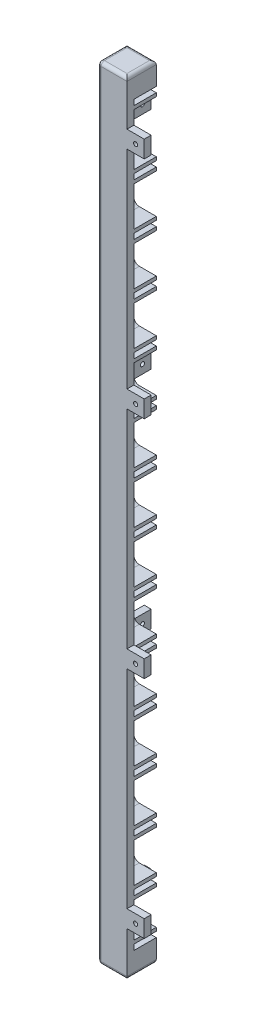
SolidWorks part; units mm, degrees
ref_plane "Front Plane" through (0, 0, 0) normal (0, 0, 1) x (1, 0, 0)
ref_plane "Top Plane" through (0, 0, 0) normal (0, 1, 0) x (1, 0, 0)
ref_plane "Right Plane" through (0, 0, 0) normal (1, 0, 0) x (0, 0, -1)
sketch "Sketch1" plane through (0, 0, 0) normal (0, 1, 0) x (1, 0, 0)
  line L1 (-3.25, -4.25) -> (4.25, -4.25)
  line L2 (-4.25, -3.25) -> (-4.25, 4.25)
  line L3 (-4.25, 4.25) -> (4.25, 4.25)
  line L4 (4.25, -4.25) -> (4.25, 4.25)
  line L5 (-4.25, -4.25) -> (4.25, 4.25) construction
  line L6 (-4.25, 4.25) -> (4.25, -4.25) construction
  arc A0 (-3.25, -4.25) -> (-4.25, -3.25) centre (-3.25, -3.25) cw
  point P0 (0, 0)
  dimension "D2" = 1
  dimension "D1" = 8.5
extrude "Boss-Extrude1" add sketch "Sketch1" along normal blind 227
fillet "Fillet1" radius 1 10 edges at (0, 0, -4.25) (-4.25, 0, -0.5) (-3.9571, 0, 3.9571) (0.5, 0, 4.25) (4.25, 0, 0) (0.5, 227, 4.25) (-3.9571, 227, 3.9571) (-4.25, 227, -0.5) (0, 227, -4.25) (4.25, 227, 0)
ref_plane "Plane1" through (0, 0, 0) normal (-0.7071, 0, -0.7071) x (-0.7071, 0, 0.7071)
sketch "Sketch2" plane through (4.25, 0, 0) normal (1, 0, 0) x (0, 0, -1)
  line L0 (-4.25, 226) -> (-4.25, 1) construction
  line L1 (-4.25, 214) -> (-2.25, 214)
  line L2 (-4.25, 214) -> (-4.25, 209)
  line L3 (-4.25, 209) -> (-2.25, 209)
  line L4 (-2.25, 214) -> (-2.25, 209)
  line L5 (-3.25, 227) -> (3.25, 227) construction
  line L6 (4.25, 113.5) -> (-4.25, 113.5) construction
  line L7 (4.25, 226) -> (4.25, 1) construction
  line L8 (-2.25, 13) -> (-2.25, 18)
  line L9 (-4.25, 18) -> (-2.25, 18)
  line L10 (-4.25, 13) -> (-4.25, 18)
  line L11 (-4.25, 13) -> (-2.25, 13)
  line L12 (-2.25, 209) -> (-2.25, 148.6667) construction
  line L13 (-4.25, 148.6667) -> (-2.25, 148.6667)
  line L14 (-4.25, 148.6667) -> (-4.25, 143.6667)
  line L15 (-4.25, 143.6667) -> (-2.25, 143.6667)
  line L16 (-2.25, 148.6667) -> (-2.25, 143.6667)
  line L17 (-4.25, 83.3333) -> (-2.25, 83.3333)
  line L18 (-4.25, 83.3333) -> (-4.25, 78.3333)
  line L19 (-4.25, 78.3333) -> (-2.25, 78.3333)
  line L20 (-2.25, 83.3333) -> (-2.25, 78.3333)
  line L21 (-2.25, 143.6667) -> (-2.25, 83.3333) construction
  dimension "D1" = 2
  dimension "D2" = 13
  dimension "D3" = 5
extrude "Boss-Extrude2" add sketch "Sketch2" along normal blind 5
hole_wizard "#0-80 Tapped Hole2" positions "3DSketch3" profile "Sketch10" tap size "#0-80" standard "ANSI Inch"
sketch3d "3DSketch3"
  line L0 (9.25, 214, 4.25) -> (4.25, 214, 4.25) construction
  line L1 (4.25, 226, 4.25) -> (4.25, 214, 4.25) construction
  line L2 (9.25, 148.6667, 4.25) -> (4.25, 148.6667, 4.25) construction
  line L3 (9.25, 83.3333, 4.25) -> (4.25, 83.3333, 4.25) construction
  line L4 (9.25, 18, 4.25) -> (4.25, 18, 4.25) construction
  point P9 (6.75, 211.5, 4.25)
  point P20 (6.75, 146.1667, 4.25)
  point P22 (6.75, 80.8333, 4.25)
  point P24 (6.75, 15.5, 4.25)
  dimension "D1" = 2.5
  dimension "D2" = 2.5
  dimension "D3" = 2.5
  dimension "D4" = 2.5
  dimension "D5" = 2.5
sketch "Sketch10" plane through (6.75, 211.5, 4.25) normal (1, 0, 0) x (0, -1, 0)
  line L0 (0, 0) -> (0, 4.3584)
  line L1 (0, 4.3584) -> (0.5956, 4.0005)
  line L2 (0.5956, 4.0005) -> (0.5956, 0)
  line L5 (0.5956, 0) -> (0, 0)
  line L10 (0, 4.3584) -> (-0.5956, 4.0005) construction
  line L11 (0, -6.35) -> (0, 107.95) construction
  dimension "Tap Drill Dia." = 1.1913
  dimension "Tap Drill Depth" = 4.0005
  dimension "Drill Angle" = 118
cosmetic thread "Hole Thread11" parameters "D1"=2, "D2"=1.524
cosmetic thread "Hole Thread12" parameters "D1"=2, "D2"=1.524
cosmetic thread "Hole Thread13" parameters "D1"=2, "D2"=1.524
cosmetic thread "Hole Thread14" parameters "D1"=2, "D2"=1.524
mirror "Mirror1" about plane through (0, 0, 0) normal (-0.7071, 0, -0.7071) of "#0-80 Tapped Hole2", "Boss-Extrude2"
sketch "Sketch3" plane through (0, 227, 0) normal (0, 1, 0) x (1, 0, 0)
  line L0 (-2.25, 9.25) -> (-2.25, 4.25) construction
  line L1 (-2.25, -2.25) -> (4.25, -2.25)
  line L2 (-2.25, -2.25) -> (-2.25, 4.25)
  line L3 (-2.25, 4.25) -> (4.25, 4.25)
  line L4 (4.25, -2.25) -> (4.25, 4.25)
  line L5 (9.25, -2.25) -> (4.25, -2.25) construction
extrude "Cut-Extrude1" cut sketch "Sketch3" against normal offset from surface (214 mm away) 6.5 from offset 6.5 up to face at (0, 0, 0) offset against normal yes
sketch "Sketch7" plane through (0, 0, 2.25) normal (0, 0, -1) x (-1, 0, 0)
  line L0 (-4.25, 148.6667) -> (-4.25, 209) construction
  line L1 (-4.25, 217.825) -> (2.25, 217.825) construction
  line L2 (-4.25, 217.825) -> (-4.25, 216.825) construction
  line L3 (-4.25, 216.825) -> (2.25, 216.825) construction
  line L4 (2.25, 217.825) -> (2.25, 216.825) construction
  line L5 (2.25, 6.5) -> (2.25, 220.5) construction
  line L6 (-3.25, 227) -> (3.25, 227) construction
  line L7 (-4.25, 215.2375) -> (2.25, 215.2375) construction
  line L8 (-4.25, 215.2375) -> (-4.25, 214.2375) construction
  line L9 (-4.25, 214.2375) -> (2.25, 214.2375) construction
  line L10 (2.25, 215.2375) -> (2.25, 214.2375) construction
  line L11 (-4.25, 12.7625) -> (2.25, 12.7625) construction
  line L12 (-4.25, 12.7625) -> (-4.25, 11.7625) construction
  line L13 (-4.25, 11.7625) -> (2.25, 11.7625) construction
  line L14 (2.25, 12.7625) -> (2.25, 11.7625) construction
  line L15 (-4.25, 10.175) -> (2.25, 10.175) construction
  line L16 (-4.25, 10.175) -> (-4.25, 9.175) construction
  line L17 (-4.25, 9.175) -> (2.25, 9.175) construction
  line L18 (2.25, 10.175) -> (2.25, 9.175) construction
  line L19 (3.25, 0) -> (-3.25, 0) construction
  line L20 (-4.25, 6.5) -> (-4.25, 13) construction
  line L21 (-4.25, 202.825) -> (2.25, 202.825)
  line L22 (-4.25, 202.825) -> (-4.25, 201.825)
  line L23 (-4.25, 201.825) -> (2.25, 201.825)
  line L24 (2.25, 202.825) -> (2.25, 201.825)
  line L25 (-4.25, 200.2375) -> (2.25, 200.2375)
  line L26 (-4.25, 200.2375) -> (-4.25, 199.2375)
  line L27 (-4.25, 199.2375) -> (2.25, 199.2375)
  line L28 (2.25, 200.2375) -> (2.25, 199.2375)
  line L29 (-4.25, 187.825) -> (2.25, 187.825)
  line L30 (-4.25, 187.825) -> (-4.25, 186.825)
  line L31 (-4.25, 186.825) -> (2.25, 186.825)
  line L32 (2.25, 187.825) -> (2.25, 186.825)
  line L33 (-4.25, 185.2375) -> (2.25, 185.2375)
  line L34 (-4.25, 185.2375) -> (-4.25, 184.2375)
  line L35 (-4.25, 184.2375) -> (2.25, 184.2375)
  line L36 (2.25, 185.2375) -> (2.25, 184.2375)
  line L37 (-4.25, 172.825) -> (2.25, 172.825)
  line L38 (-4.25, 172.825) -> (-4.25, 171.825)
  line L39 (-4.25, 171.825) -> (2.25, 171.825)
  line L40 (2.25, 172.825) -> (2.25, 171.825)
  line L41 (-4.25, 170.2375) -> (2.25, 170.2375)
  line L42 (-4.25, 170.2375) -> (-4.25, 169.2375)
  line L43 (-4.25, 169.2375) -> (2.25, 169.2375)
  line L44 (2.25, 170.2375) -> (2.25, 169.2375)
  line L45 (-4.25, 157.825) -> (2.25, 157.825)
  line L46 (-4.25, 157.825) -> (-4.25, 156.825)
  line L47 (-4.25, 156.825) -> (2.25, 156.825)
  line L48 (2.25, 157.825) -> (2.25, 156.825)
  line L49 (-4.25, 155.2375) -> (2.25, 155.2375)
  line L50 (-4.25, 155.2375) -> (-4.25, 154.2375)
  line L51 (-4.25, 154.2375) -> (2.25, 154.2375)
  line L52 (2.25, 155.2375) -> (2.25, 154.2375)
  line L53 (-4.25, 142.825) -> (2.25, 142.825)
  line L54 (-4.25, 142.825) -> (-4.25, 141.825)
  line L55 (-4.25, 141.825) -> (2.25, 141.825)
  line L56 (2.25, 142.825) -> (2.25, 141.825)
  line L57 (-4.25, 140.2375) -> (2.25, 140.2375)
  line L58 (-4.25, 140.2375) -> (-4.25, 139.2375)
  line L59 (-4.25, 139.2375) -> (2.25, 139.2375)
  line L60 (2.25, 140.2375) -> (2.25, 139.2375)
  line L61 (-4.25, 127.825) -> (2.25, 127.825)
  line L62 (-4.25, 127.825) -> (-4.25, 126.825)
  line L63 (-4.25, 126.825) -> (2.25, 126.825)
  line L64 (2.25, 127.825) -> (2.25, 126.825)
  line L65 (-4.25, 125.2375) -> (2.25, 125.2375)
  line L66 (-4.25, 125.2375) -> (-4.25, 124.2375)
  line L67 (-4.25, 124.2375) -> (2.25, 124.2375)
  line L68 (2.25, 125.2375) -> (2.25, 124.2375)
  line L69 (-4.25, 112.825) -> (2.25, 112.825)
  line L70 (-4.25, 112.825) -> (-4.25, 111.825)
  line L71 (-4.25, 111.825) -> (2.25, 111.825)
  line L72 (2.25, 112.825) -> (2.25, 111.825)
  line L73 (-4.25, 110.2375) -> (2.25, 110.2375)
  line L74 (-4.25, 110.2375) -> (-4.25, 109.2375)
  line L75 (-4.25, 109.2375) -> (2.25, 109.2375)
  line L76 (2.25, 110.2375) -> (2.25, 109.2375)
  line L77 (-4.25, 97.825) -> (2.25, 97.825)
  line L78 (-4.25, 97.825) -> (-4.25, 96.825)
  line L79 (-4.25, 96.825) -> (2.25, 96.825)
  line L80 (2.25, 97.825) -> (2.25, 96.825)
  line L81 (-4.25, 95.2375) -> (2.25, 95.2375)
  line L82 (-4.25, 95.2375) -> (-4.25, 94.2375)
  line L83 (-4.25, 94.2375) -> (2.25, 94.2375)
  line L84 (2.25, 95.2375) -> (2.25, 94.2375)
  line L85 (-4.25, 82.825) -> (2.25, 82.825)
  line L86 (-4.25, 82.825) -> (-4.25, 81.825)
  line L87 (-4.25, 81.825) -> (2.25, 81.825)
  line L88 (2.25, 82.825) -> (2.25, 81.825)
  line L89 (-4.25, 80.2375) -> (2.25, 80.2375)
  line L90 (-4.25, 80.2375) -> (-4.25, 79.2375)
  line L91 (-4.25, 79.2375) -> (2.25, 79.2375)
  line L92 (2.25, 80.2375) -> (2.25, 79.2375)
  line L93 (-4.25, 67.825) -> (2.25, 67.825)
  line L94 (-4.25, 67.825) -> (-4.25, 66.825)
  line L95 (-4.25, 66.825) -> (2.25, 66.825)
  line L96 (2.25, 67.825) -> (2.25, 66.825)
  line L97 (-4.25, 65.2375) -> (2.25, 65.2375)
  line L98 (-4.25, 65.2375) -> (-4.25, 64.2375)
  line L99 (-4.25, 64.2375) -> (2.25, 64.2375)
  line L100 (2.25, 65.2375) -> (2.25, 64.2375)
  line L101 (-4.25, 52.825) -> (2.25, 52.825)
  line L102 (-4.25, 52.825) -> (-4.25, 51.825)
  line L103 (-4.25, 51.825) -> (2.25, 51.825)
  line L104 (2.25, 52.825) -> (2.25, 51.825)
  line L105 (-4.25, 50.2375) -> (2.25, 50.2375)
  line L106 (-4.25, 50.2375) -> (-4.25, 49.2375)
  line L107 (-4.25, 49.2375) -> (2.25, 49.2375)
  line L108 (2.25, 50.2375) -> (2.25, 49.2375)
  line L109 (-4.25, 37.825) -> (2.25, 37.825)
  line L110 (-4.25, 37.825) -> (-4.25, 36.825)
  line L111 (-4.25, 36.825) -> (2.25, 36.825)
  line L112 (2.25, 37.825) -> (2.25, 36.825)
  line L113 (-4.25, 35.2375) -> (2.25, 35.2375)
  line L114 (-4.25, 35.2375) -> (-4.25, 34.2375)
  line L115 (-4.25, 34.2375) -> (2.25, 34.2375)
  line L116 (2.25, 35.2375) -> (2.25, 34.2375)
  line L117 (-4.25, 22.825) -> (2.25, 22.825)
  line L118 (-4.25, 22.825) -> (-4.25, 21.825)
  line L119 (-4.25, 21.825) -> (2.25, 21.825)
  line L120 (2.25, 22.825) -> (2.25, 21.825)
  line L121 (-4.25, 20.2375) -> (2.25, 20.2375)
  line L122 (-4.25, 20.2375) -> (-4.25, 19.2375)
  line L123 (-4.25, 19.2375) -> (2.25, 19.2375)
  line L124 (2.25, 20.2375) -> (2.25, 19.2375)
  line L125 (-4.25, 226) -> (-4.25, 214) construction
  line L126 (-4.25, 8.0875) -> (2.25, 8.0875)
  line L127 (-4.25, 8.0875) -> (-4.25, 9.0875)
  line L128 (-4.25, 9.0875) -> (2.25, 9.0875)
  line L129 (2.25, 8.0875) -> (2.25, 9.0875)
  line L130 (-4.25, 214) -> (-4.25, 220.5) construction
  line L131 (-4.25, 218.9125) -> (2.25, 218.9125)
  line L132 (-4.25, 218.9125) -> (-4.25, 217.9125)
  line L133 (-4.25, 217.9125) -> (2.25, 217.9125)
  line L134 (2.25, 218.9125) -> (2.25, 217.9125)
  line L135 (2.25, 220.5) -> (-4.25, 220.5) construction
  line L136 (2.25, 6.5) -> (-4.25, 6.5) construction
  dimension "D1" = 1
  dimension "D2" = 1.5875
  dimension "D3" = 10.175
  dimension "D5" = 10.175
  dimension "D7" = 11.4125
  dimension "D8" = 1.5875
  dimension "D9" = 1.5875
  dimension "D4" = 2
  dimension "D6" = 14
extrude "Boss-Extrude5" add sketch "Sketch7" along normal up to surface (6.5 mm away) up to face at (-0.75, 220.1667, -4.25)
fillet "Fillet4" radius 0.5 30 edges at (-2.25, 21.825, -1) (-2.25, 20.2375, -1) (-2.25, 35.2375, -1) (-2.25, 36.825, -1) (-2.25, 51.825, -1) (-2.25, 50.2375, -1) (-2.25, 65.2375, -1) (-2.25, 66.825, -1) (-2.25, 81.825, -1) (-2.25, 80.2375, -1) (-2.25, 95.2375, -1) (-2.25, 96.825, -1) (-2.25, 111.825, -1) (-2.25, 110.2375, -1) (-2.25, 125.2375, -1) (-2.25, 126.825, -1) (-2.25, 141.825, -1) (-2.25, 140.2375, -1) (-2.25, 156.825, -1) (-2.25, 155.2375, -1) (-2.25, 170.2375, -1) (-2.25, 171.825, -1) (-2.25, 186.825, -1) (-2.25, 185.2375, -1) (-2.25, 200.2375, -1) (-2.25, 201.825, -1) (-2.25, 220.5, -1) (-2.25, 218.9125, -1) (-2.25, 6.5, -1) (-2.25, 8.0875, -1)
fillet "Fillet5" radius 1.5875 28 edges at (-2.25, 19.2375, -1) (-2.25, 199.2375, -1) (-2.25, 184.2375, -1) (-2.25, 202.825, -1) (-2.25, 187.825, -1) (-2.25, 172.825, -1) (-2.25, 157.825, -1) (-2.25, 169.2375, -1) (-2.25, 154.2375, -1) (-2.25, 139.2375, -1) (-2.25, 124.2375, -1) (-2.25, 109.2375, -1) (-2.25, 94.2375, -1) (-2.25, 79.2375, -1) (-2.25, 127.825, -1) (-2.25, 112.825, -1) (-2.25, 97.825, -1) (-2.25, 82.825, -1) (-2.25, 67.825, -1) (-2.25, 52.825, -1) (-2.25, 37.825, -1) (-2.25, 64.2375, -1) (-2.25, 49.2375, -1) (-2.25, 34.2375, -1) (-2.25, 22.825, -1) (-2.25, 9.0875, -1) (-2.25, 217.9125, -1) (-2.25, 142.825, -1)
sketch "Sketch8" plane through (0, 0, -9.25) normal (0, 0, -1) x (-1, 0, 0)
  line L1 (2.2109, 18) -> (4.25, 18) construction
  line L2 (4.25, 13) -> (2.25, 13)
  line L3 (4.25, 13) -> (4.25, 18)
  line L4 (4.25, 18) -> (2.25, 18)
  line L5 (2.25, 13) -> (2.25, 18)
  line L6 (4.25, 214) -> (2.25, 214)
  line L7 (4.25, 214) -> (4.25, 209)
  line L8 (4.25, 209) -> (2.25, 209)
  line L9 (2.25, 214) -> (2.25, 209)
  line L10 (2.25, 13) -> (2.25, 17.65) construction
  line L11 (2.25, 144.4125) -> (2.25, 148.6667) construction
  line L12 (4.25, 148.6667) -> (2.25, 148.6667)
  line L13 (4.25, 148.6667) -> (4.25, 143.6667)
  line L14 (4.25, 143.6667) -> (2.25, 143.6667)
  line L15 (2.25, 148.6667) -> (2.25, 143.6667)
  line L16 (4.25, 83.3333) -> (2.25, 83.3333)
  line L17 (4.25, 83.3333) -> (4.25, 78.3333)
  line L18 (4.25, 78.3333) -> (2.25, 78.3333)
  line L19 (2.25, 83.3333) -> (2.25, 78.3333)
  line L20 (4.25, 143.6667) -> (2.0639, 143.6667) construction
extrude "Cut-Extrude2" cut sketch "Sketch8" against normal up to surface (5 mm away) flip side to cut up to face at (-0.3999, 219.2859, -4.25)
